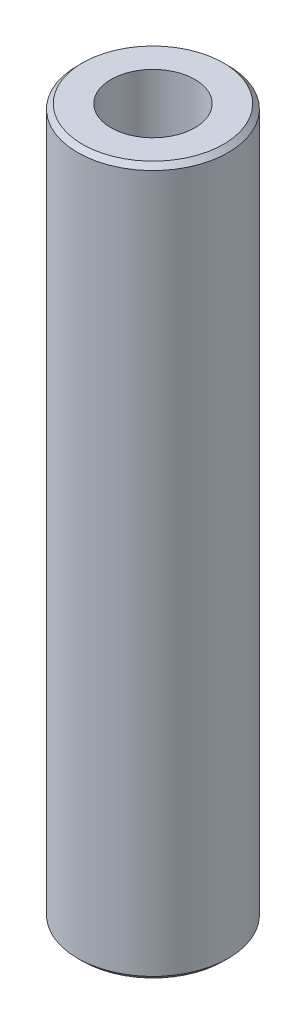
SolidWorks part; units mm, degrees
ref_plane "Front Plane" through (0, 0, 0) normal (0, 0, 1) x (1, 0, 0)
ref_plane "Top Plane" through (0, 0, 0) normal (0, 1, 0) x (1, 0, 0)
ref_plane "Right Plane" through (0, 0, 0) normal (1, 0, 0) x (0, 0, -1)
sketch "Sketch1" plane through (0, 0, 0) normal (0, 1, 0) x (1, 0, 0)
  circle A0 centre (0, 0) radius 42.5
  dimension "SHAFT_OD" = 85
extrude "Boss-Extrude1" add sketch "Sketch1" along normal blind 399.1804
sketch "Sketch2" plane through (0, 0, 0) normal (0, 1, 0) x (1, 0, 0)
  circle A0 centre (0, 0) radius 23.6495
  dimension "BORE_D" = 47.2991
extrude "Cut-Extrude1" cut sketch "Sketch2" along normal through all
chamfer "Chamfer1" distance 2.6908 angle 45 2 edges at (0, 399.1804, 42.5) (0, 0, 42.5)
